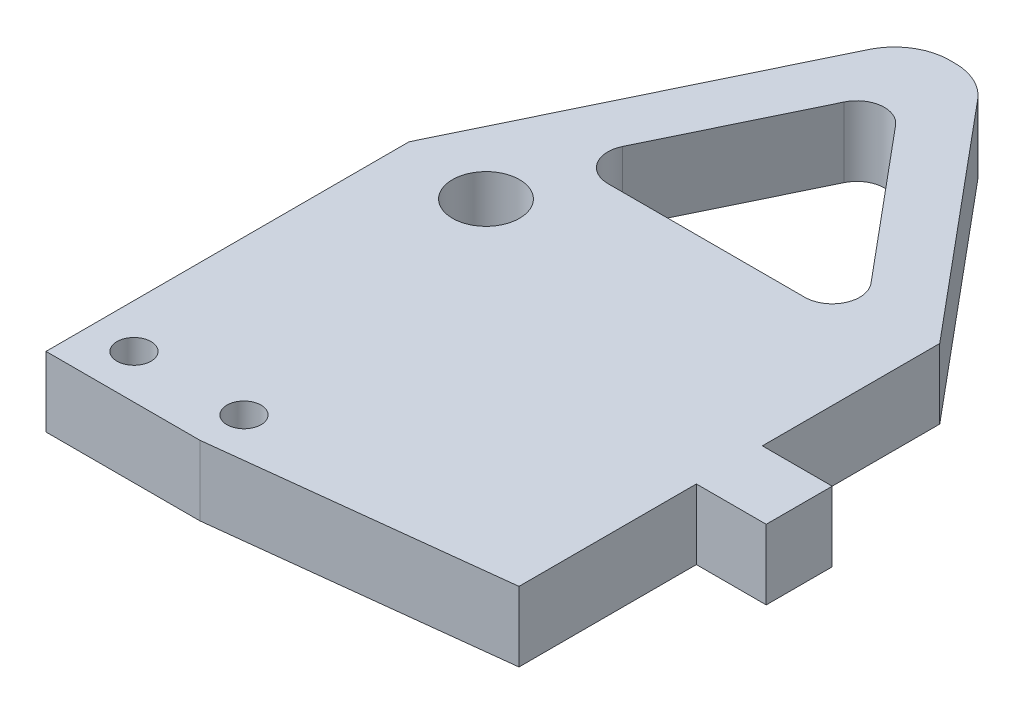
SolidWorks part; units mm, degrees
material "6061 Alloy"
ref_plane "Front Plane" through (0, 0, 0) normal (0, 0, 1) x (1, 0, 0)
ref_plane "Top Plane" through (0, 0, 0) normal (0, 1, 0) x (1, 0, 0)
ref_plane "Right Plane" through (0, 0, 0) normal (1, 0, 0) x (0, 0, -1)
sketch "Sketch1" plane through (0, 0, 0) normal (0, 1, 0) x (1, 0, 0)
  line L1 (-80, 0) -> (-80, 60)
  line L7 (0, 0) -> (-52, -6)
  line L8 (-52, -6) -> (-80, -6)
  line L9 (-80, -6) -> (-80, 0)
  line L10 (-80, 60) -> (-50, 122)
  line L11 (-50, 122) -> (-38, 122)
  line L12 (-38, 122) -> (0, 76.5)
  line L13 (0, 76.5) -> (0, 44.25)
  line L14 (0, 44.25) -> (12.7, 44.25)
  line L15 (12.7, 44.25) -> (12.7, 32.25)
  line L16 (12.7, 32.25) -> (0, 32.25)
  line L17 (0, 32.25) -> (0, 0)
  circle A0 centre (-64, 58) radius 6.1
  circle A3 centre (-72, 2) radius 3.1
  circle A4 centre (-52, 2) radius 3.1
  dimension "D8" = 12.2
  dimension "D11" = 32.25
  dimension "D12" = 6.2
  dimension "D16" = 6.2
  dimension "D1" = 80
  dimension "D2" = 76.5
  dimension "D3" = 60
  dimension "D4" = 62
  dimension "D5" = 30
  dimension "D6" = 12
  dimension "D7" = 32.25
  dimension "D9" = 16
  dimension "D10" = 6
  dimension "D13" = 8
  dimension "D14" = 8
  dimension "D15" = 20
  dimension "D17" = 58
  dimension "D18" = 12.7
extrude "Boss-Extrude1" add sketch "Sketch1" along normal blind 12.7
fillet "Fillet1" radius 10 2 edges at (-38, 6.35, -122) (-50, 6.35, -122)
sketch "Sketch3" plane through (0, 12.7, 0) normal (0, 1, 0) x (1, 0, 0)
  line L5 (-8.853, 71.5) -> (-43.3435, 112.7979)
  line L6 (-43.3435, 112.7979) -> (-63.3263, 71.5)
  line L7 (-63.3263, 71.5) -> (-8.853, 71.5)
  line L10 (0, 76.5) -> (-35.0019, 118.4101) construction
  line L11 (-52.7312, 116.3556) -> (-80, 60) construction
  dimension "D1" = 10
  dimension "D2" = 10
  dimension "D3" = 10
  dimension "D4" = 10
  dimension "D5" = 5
extrude "Cut-Extrude1" cut sketch "Sketch3" against normal through all
fillet "Fillet2" radius 5 3 edges at (-43.3435, 6.35, -112.7979) (-8.853, 6.35, -71.5) (-63.3263, 6.35, -71.5)
